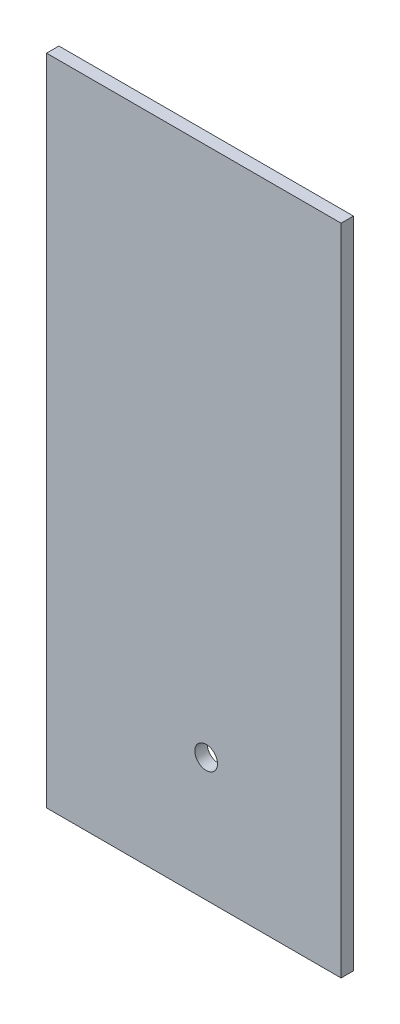
SolidWorks part; units mm, degrees
material "Perspex (TM) GS Acrylic Cast Sheet"
ref_plane "Front Plane" through (0, 0, 0) normal (0, 0, 1) x (1, 0, 0)
ref_plane "Top Plane" through (0, 0, 0) normal (0, 1, 0) x (1, 0, 0)
ref_plane "Right Plane" through (0, 0, 0) normal (1, 0, 0) x (0, 0, -1)
sketch "Sketch1" plane through (0, 0, 0) normal (0, 0, 1) x (1, 0, 0)
  line L1 (-71.5, -158.685) -> (71.5, -158.685)
  line L2 (-71.5, -158.685) -> (-71.5, 158.685)
  line L3 (-71.5, 158.685) -> (71.5, 158.685)
  line L4 (71.5, -158.685) -> (71.5, 158.685)
  line L5 (-71.5, -158.685) -> (71.5, 158.685) construction
  line L6 (-71.5, 158.685) -> (71.5, -158.685) construction
  point P0 (0, 0)
  dimension "D1" = 143
  dimension "D2" = 317.37
extrude "Boss-Extrude1" add sketch "Sketch1" along normal blind 6
sketch "Sketch2" plane through (0, 0, 6) normal (0, 0, 1) x (1, 0, 0)
  line L0 (6, -158.685) -> (6, -98.685) construction
  line L2 (-71.5, -158.685) -> (71.5, -158.685) construction
  circle A0 centre (6, -98.685) radius 5.5
  point P2 (0, -150.7481)
  point P3 (26.289, -158.685)
  point P6 (0, 0)
  point P8 (0, 0)
  point P10 (0, -158.685)
  dimension "D2" = 11
  dimension "D1" = 60
  dimension "D3" = 6
extrude "Cut-Extrude1" cut sketch "Sketch2" against normal through all
equation "\"PCLength\"= 143mm'Length across I/O from PS to GPU"
equation "\"PCWidth\"= 340mm'Distance of longest part parallel to GPU(ussually GPU)"
equation "\"PCHeight\"= 190mm'Tallest point with mobo laying flat"
equation "\"WallThickness\"= 9mm'Thickness of each outer tank wall"
equation "\"ThermoBarrierThickness\"= 6mm'Thickness of barrier between hot side and cold side"
equation "\"HotSideGap\"= 15mm'Space in the hot side that hot fluid flows into"
equation "\"PCClearance\"= 40mm'Clearance from top of tank to top of PC"
equation "\"RadiatorHeight\"= 277.37mm'Final Height from ground of radiators"
equation "\"D1@Sketch1\"=\"PCLength\""
equation "\"D2@Sketch1\"=\"RadiatorHeight\" + 40"
equation "\"D1@Boss-Extrude1\"=\"ThermoBarrierThickness\""
